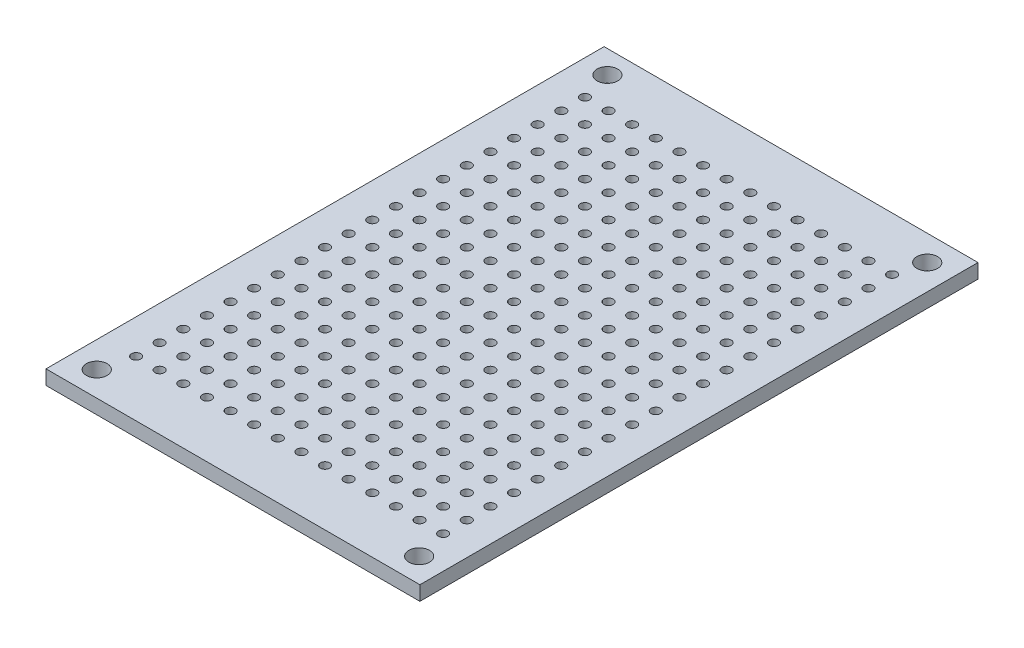
SolidWorks part; units mm, degrees
ref_plane "Front Plane" through (0, 0, 0) normal (0, 0, 1) x (1, 0, 0)
ref_plane "Top Plane" through (0, 0, 0) normal (0, 1, 0) x (1, 0, 0)
ref_plane "Right Plane" through (0, 0, 0) normal (1, 0, 0) x (0, 0, -1)
sketch "Sketch1" plane through (0, 0, 0) normal (0, 1, 0) x (1, 0, 0)
  line L1 (-20.1, -30) -> (20.1, -30)
  line L2 (-20.1, -30) -> (-20.1, 30)
  line L3 (-20.1, 30) -> (20.1, 30)
  line L4 (20.1, -30) -> (20.1, 30)
  line L5 (-20.1, -30) -> (20.1, 30) construction
  line L6 (-20.1, 30) -> (20.1, -30) construction
  line L7 (-18.39, 26.43) -> (-16.17, 26.43) construction
  line L8 (-18.39, 26.43) -> (-18.39, 28.65) construction
  line L9 (-18.39, 28.65) -> (-16.17, 28.65) construction
  line L10 (-16.17, 26.43) -> (-16.17, 28.65) construction
  line L11 (-18.39, 26.43) -> (-16.17, 28.65) construction
  line L12 (-18.39, 28.65) -> (-16.17, 26.43) construction
  line L13 (16.26, 26.16) -> (18.48, 26.16) construction
  line L14 (16.26, 26.16) -> (16.26, 28.38) construction
  line L15 (16.26, 28.38) -> (18.48, 28.38) construction
  line L16 (18.48, 26.16) -> (18.48, 28.38) construction
  line L17 (16.26, 26.16) -> (18.48, 28.38) construction
  line L18 (16.26, 28.38) -> (18.48, 26.16) construction
  line L19 (16.1168, -28.5) -> (18.7, -28.5) construction
  line L20 (16.1168, -28.5) -> (16.1168, -26.28) construction
  line L21 (16.1168, -26.28) -> (18.7, -26.28) construction
  line L22 (18.7, -28.5) -> (18.7, -26.28) construction
  line L23 (16.1168, -28.5) -> (18.7, -26.28) construction
  line L24 (16.1168, -26.28) -> (18.7, -28.5) construction
  line L25 (-18.58, -28.45) -> (-16.0282, -28.45) construction
  line L26 (-18.58, -28.45) -> (-18.58, -26.23) construction
  line L27 (-18.58, -26.23) -> (-16.0282, -26.23) construction
  line L28 (-16.0282, -28.45) -> (-16.0282, -26.23) construction
  line L29 (-18.58, -28.45) -> (-16.0282, -26.23) construction
  line L30 (-18.58, -26.23) -> (-16.0282, -28.45) construction
  circle A0 centre (-17.28, 27.54) radius 1.11
  circle A1 centre (17.37, 27.27) radius 1.11
  circle A2 centre (17.4084, -27.39) radius 1.11
  circle A3 centre (-17.3041, -27.34) radius 1.11
  point P0 (0, 0)
  dimension "D4" = 2.22
  dimension "D6" = 2.22
  dimension "D9" = 2.22
  dimension "D10" = 1.4
  dimension "D12" = 2.22
  dimension "D1" = 40.2
  dimension "D2" = 60
  dimension "D3" = 1.71
  dimension "D5" = 1.35
  dimension "D7" = 1.62
  dimension "D8" = 1.62
  dimension "D11" = 1.5
  dimension "D13" = 1.52
  dimension "D14" = 1.55
extrude "Boss-Extrude1" add sketch "Sketch1" along normal blind 1.55
sketch "Sketch2" plane through (0, 1.55, 0) normal (0, 1, 0) x (1, 0, 0)
  line L0 (20.1, -30) -> (20.1, 30) construction
  line L1 (16.1, -24.5) -> (17.1, -24.5) construction
  line L2 (16.1, -24.5) -> (16.1, -23.5) construction
  line L3 (16.1, -23.5) -> (17.1, -23.5) construction
  line L4 (17.1, -24.5) -> (17.1, -23.5) construction
  line L5 (16.1, -24.5) -> (17.1, -23.5) construction
  line L6 (16.1, -23.5) -> (17.1, -24.5) construction
  line L7 (-20.1, -30) -> (20.1, -30) construction
  circle A0 centre (16.6, -24) radius 0.5
  dimension "D1" = 1
  dimension "D2" = 3
  dimension "D3" = 5.5
extrude "Cut-Extrude1" cut sketch "Sketch2" against normal blind 1.55
pattern_linear "LPattern1" count 14 spacing 2.54 along (-1, 0, 0) count 20 spacing 2.54 along (0, 0, -1) of "Cut-Extrude1"
